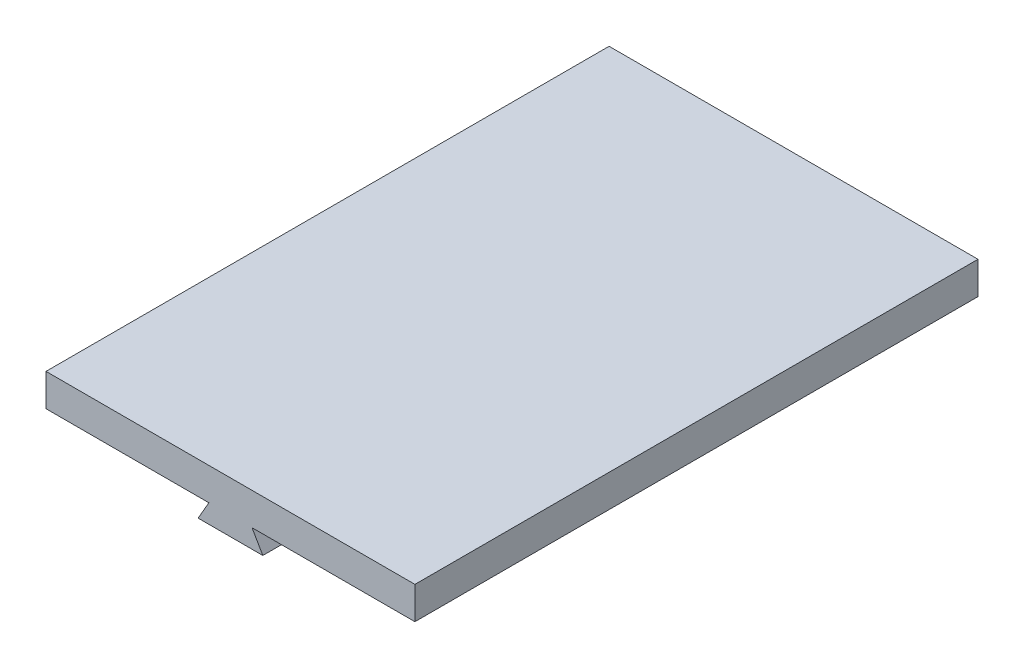
SolidWorks part; units mm, degrees
ref_plane "Front Plane" through (0, 0, 0) normal (0, 0, 1) x (1, 0, 0)
ref_plane "Top Plane" through (0, 0, 0) normal (0, 1, 0) x (1, 0, 0)
ref_plane "Right Plane" through (0, 0, 0) normal (1, 0, 0) x (0, 0, -1)
sketch "Sketch1" plane through (0, 0, 0) normal (0, 1, 0) x (1, 0, 0)
  line L0 (-28.5, -43.5) -> (28.5, -43.5)
  line L1 (-28.5, -43.5) -> (-28.5, 43.5)
  line L2 (-28.5, 43.5) -> (28.5, 43.5)
  line L3 (28.5, -43.5) -> (28.5, 43.5)
  line L4 (-28.5, -43.5) -> (28.5, 43.5) construction
  line L5 (-28.5, 43.5) -> (28.5, -43.5) construction
  point P0 (0, 0)
  point P5 (0, 0)
  dimension "D1" = 87
  dimension "D2" = 57
extrude "Boss-Extrude1" add sketch "Sketch1" along normal blind 5 contours L2 L3 L0 L1
sketch "Sketch2" plane through (0, 0, 43.5) normal (0, 0, 1) x (1, 0, 0)
  line L0 (-28.5, 0) -> (28.5, 0) construction
  line L1 (0, 5.7735) -> (-5, -2.8868)
  line L2 (-5, -2.8868) -> (5, -2.8868)
  line L3 (5, -2.8868) -> (0, 5.7735)
  line L4 (-3.3333, 0) -> (3.3333, 0)
  circle A0 centre (0, 0) radius 2.8868 construction
  line M2 (-28.5, 0) -> (28.5, 0)
  dimension "D1" = 10
extrude "Boss-Extrude2" add sketch "Sketch2" against normal blind 5 contours L2 L3 L1 M2 region at (0, -1.5396, 43.5)
extrude "Boss-Extrude3" add sketch "Sketch2<3>" along normal blind 5 from surface contours L2 L3 L1 M2 region at (0, -1.5396, 43.5) starting at face at (0, 2.5, -43.5)
sketch "Sketch2<3>" plane through (0, 0, 43.5) normal (0, 0, 1) x (1, 0, 0) same geometry as "Sketch2"
